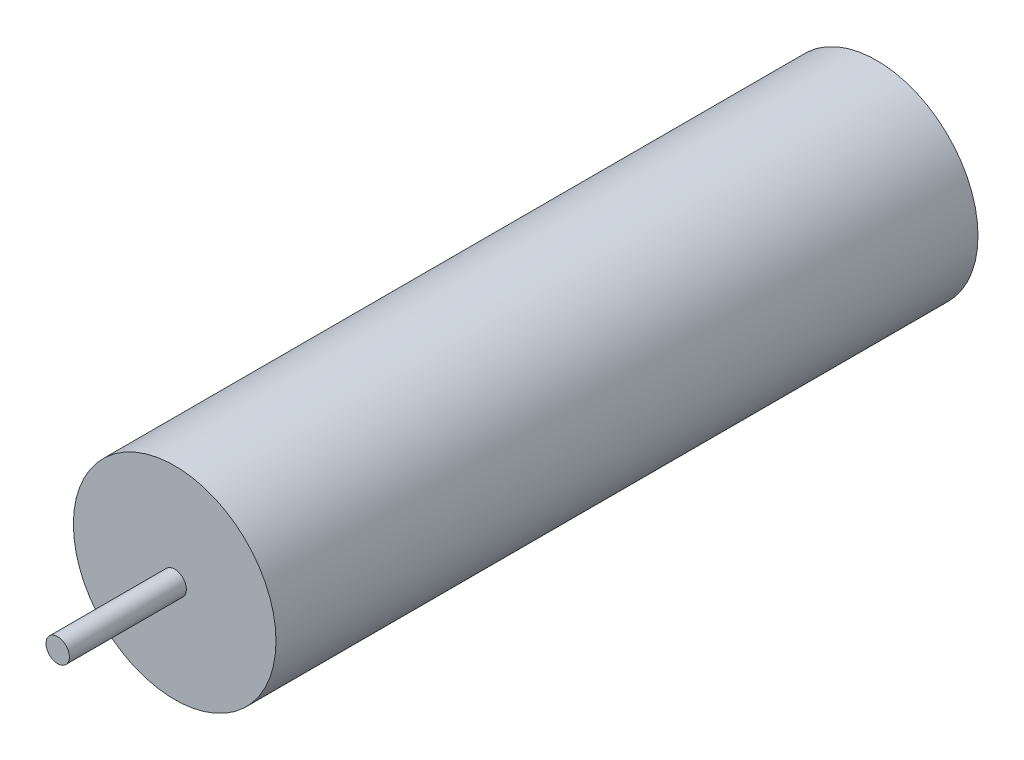
SolidWorks part; units mm, degrees
material "1023 Carbon Steel Sheet (SS)"
ref_plane "Front Plane" through (0, 0, 0) normal (0, 0, 1) x (1, 0, 0)
ref_plane "Top Plane" through (0, 0, 0) normal (0, 1, 0) x (1, 0, 0)
ref_plane "Right Plane" through (0, 0, 0) normal (1, 0, 0) x (0, 0, -1)
sketch "Sketch1" plane through (0, 0, 0) normal (0, 0, 1) x (1, 0, 0)
  circle A0 centre (0, -25.4) radius 10.9982
  circle A1 centre (0, -25.4) radius 10.9982 construction
  point P3 (-7.9607, -45.249)
extrude "Boss-Extrude1" add sketch "Sketch1" against normal blind 76.2
sketch "Sketch2" plane through (0, 0, 0) normal (0, 0, 1) x (1, 0, 0)
  circle A0 centre (0, -25.4) radius 1.27
  dimension "D1" = 2.54
extrude "Boss-Extrude2" add sketch "Sketch2" along normal blind 12.7
